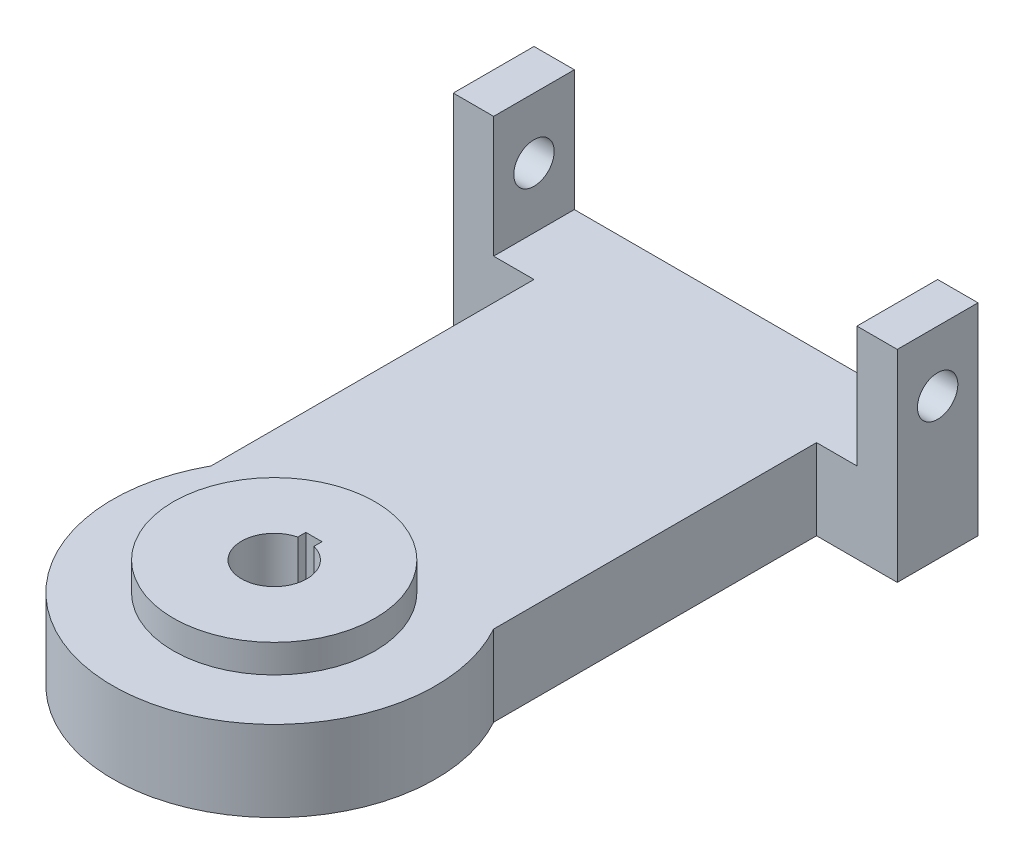
SolidWorks part; units mm, degrees
ref_plane "Front Plane" through (0, 0, 0) normal (0, 0, 1) x (1, 0, 0)
ref_plane "Top Plane" through (0, 0, 0) normal (0, 1, 0) x (1, 0, 0)
ref_plane "Right Plane" through (0, 0, 0) normal (1, 0, 0) x (0, 0, -1)
sketch "Sketch1" plane through (0, 0, 0) normal (0, 1, 0) x (1, 0, 0)
  circle A21 centre (0, 0) radius 20
  dimension "D1" = 40
extrude "Boss-Extrude1" add sketch "Sketch1" along normal blind 10
sketch "Sketch2" plane through (0, 10, 0) normal (0, 1, 0) x (1, 0, 0)
  line L0 (-1, 3.9246) -> (-1, 4.9246)
  line L1 (-1, 4.9246) -> (1, 4.9246)
  line L2 (1, 4.9246) -> (1, 3.9246)
  arc A1 (-1, 3.9246) -> (1, 3.9246) centre (0, 0) ccw
  point P4 (0, 4.9246)
  dimension "D1" = 8.1
  dimension "D2" = 1
  dimension "D3" = 2
extrude "Cut-Extrude1" cut sketch "Sketch2" against normal offset from surface (2.5 mm away) 7.5 up to face at (0, 0, 20)
sketch "Sketch3" plane through (0, 0, 0) normal (0, 1, 0) x (1, 0, 0)
  line L0 (-17.5, 59.6825) -> (-17.5, 9.6825)
  line L1 (-17.5, 59.6825) -> (17.5, 59.6825)
  line L2 (17.5, 59.6825) -> (17.5, 9.6825)
  circle A0 centre (0, 0) radius 20 construction
  arc A1 (17.5, 9.6825) -> (-17.5, 9.6825) centre (0, 0) ccw
  point P6 (0, 59.6825)
  point P9 (0, 20)
  dimension "D1" = 35
  dimension "D2" = 50
extrude "Boss-Extrude2" add sketch "Sketch3" along normal up to surface (10 mm away) up to face at (0, 10, -2.431)
sketch "Sketch6" plane through (0, 10, 0) normal (0, 1, 0) x (1, 0, 0)
  line L0 (-1, 4.9246) -> (1, 4.9246)
  line L1 (1, 4.9246) -> (1, 3.9246)
  line L2 (1, 3.9246) -> (1, 4.9246) construction
  line L3 (-1, 4.9246) -> (-1, 3.9246)
  line L4 (-1, 4.9246) -> (-1, 3.9246) construction
  circle A0 centre (0, 0) radius 12.5
  arc A1 (-1, 3.9246) -> (1, 3.9246) centre (0, 0) ccw
  arc A2 (-1, 3.9246) -> (1, 3.9246) centre (0, 0) ccw construction
  dimension "D1" = 25
extrude "Boss-Extrude3" add sketch "Sketch6" along normal blind 6
sketch "Sketch7" plane through (0, 0, -59.6825) normal (0, 0, -1) x (-1, 0, 0)
  line L0 (-27.5, 0) -> (-27.5, 25)
  line L1 (-27.5, 25) -> (-22.5, 25)
  line L2 (-22.5, 25) -> (-22.5, 10)
  line L3 (-17.5, 10) -> (17.5, 10) construction
  line L4 (-22.5, 10) -> (22.5, 10)
  line L5 (22.5, 10) -> (22.5, 25)
  line L6 (22.5, 25) -> (27.5, 25)
  line L7 (27.5, 25) -> (27.5, 0)
  line L8 (27.5, 0) -> (-27.5, 0)
  dimension "D1" = 5
  dimension "D2" = 15
  dimension "D3" = 45
extrude "Boss-Extrude4" add sketch "Sketch7" against normal blind 10
sketch "Sketch8" plane through (-27.5, 0, 0) normal (-1, 0, 0) x (0, 0, 1)
  line L1 (-49.6825, 25) -> (-59.6825, 25) construction
  circle A0 centre (-54.6825, 17.5) radius 2.5
  point P7 (-54.6825, 25)
  dimension "D2" = 5
  dimension "D1" = 7.5
extrude "Cut-Extrude2" cut sketch "Sketch8" against normal through all
sketch "Sketch9" plane through (0, 16, 0) normal (0, 1, 0) x (1, 0, 0)
  circle A0 centre (0, 0) radius 12.5
  circle A1 centre (0, 0) radius 12.5 construction
extrude "Cut-Extrude3" cut sketch "Sketch9" against normal blind 2.5
